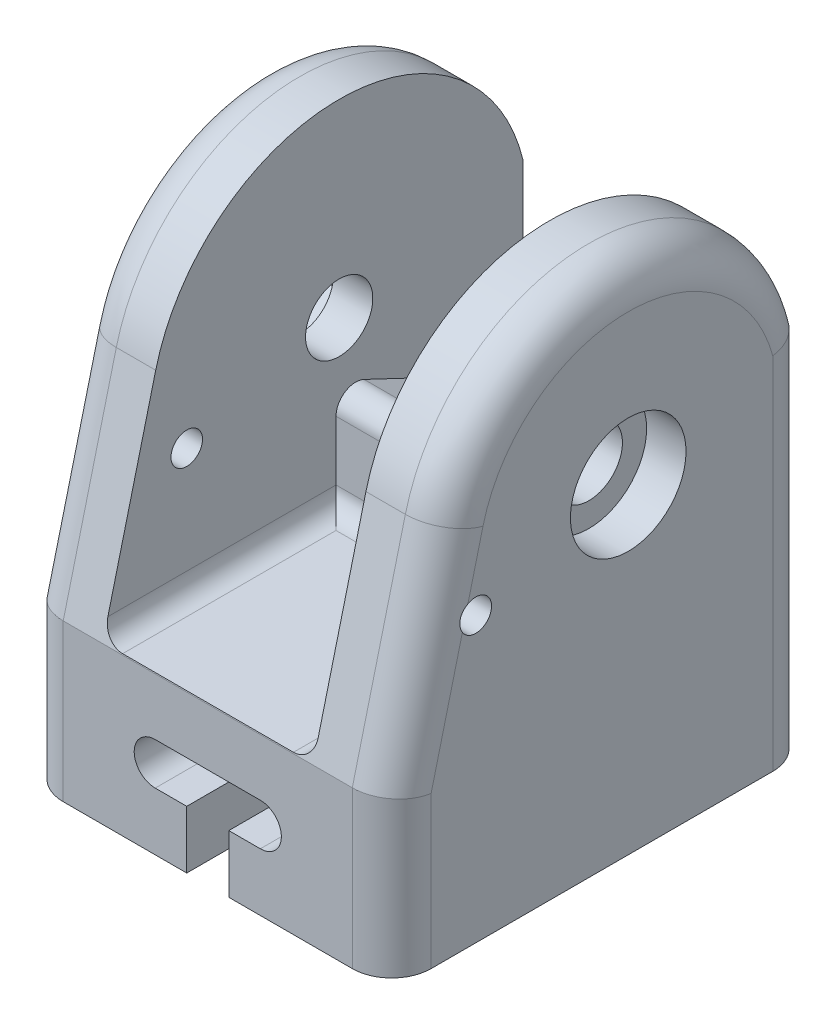
SolidWorks part; units mm, degrees
ref_plane "Front Plane" through (0, 0, 0) normal (0, 0, 1) x (1, 0, 0)
ref_plane "Top Plane" through (0, 0, 0) normal (0, 1, 0) x (1, 0, 0)
ref_plane "Right Plane" through (0, 0, 0) normal (1, 0, 0) x (0, 0, -1)
sketch "Sketch2" plane through (0, 0, 0) normal (0, 1, 0) x (1, 0, 0)
  line L0 (5, 10) -> (8.75, 10)
  line L1 (-8.75, -10) -> (8.75, -10)
  line L2 (-8.75, -10) -> (-8.75, 10)
  line L3 (-8.75, 10) -> (-5, 10)
  line L4 (8.75, -10) -> (8.75, 10)
  line L5 (-8.75, -10) -> (8.75, 10) construction
  line L6 (-8.75, 10) -> (8.75, -10) construction
  line L8 (-5, 10) -> (-5, 5)
  line L9 (-5, 5) -> (5, 5)
  line L10 (5, 10) -> (5, 5)
  point P0 (0, 0)
  point P15 (-5, 5)
  dimension "D1" = 17.5
  dimension "D2" = 20
  dimension "D3" = 3.75
  dimension "D4" = 5
extrude "Boss-Extrude1" add sketch "Sketch2" along normal blind 22.5
sketch "Sketch3" plane through (0, 22.5, 0) normal (0, 1, 0) x (1, 0, 0)
  line L0 (-8.75, -10) -> (8.75, -10) construction
  line L1 (-5, 10) -> (5, 10)
  line L2 (-5, 10) -> (-5, -10)
  line L3 (-5, -10) -> (5, -10)
  line L4 (5, 10) -> (5, -10)
  line L5 (5, 10) -> (5, 5) construction
extrude "Cut-Extrude1" cut sketch "Sketch3" against normal blind 17.5
sketch "Sketch4" plane through (8.75, 0, 0) normal (1, 0, 0) x (0, 0, -1)
  line L0 (10, 22.5) -> (10, 0) construction
  line L1 (-10, 22.5) -> (10, 22.5) construction
  line L2 (10, 14.8565) -> (10, 0)
  line L3 (10, 0) -> (-10, 0)
  line L4 (-10, 0) -> (-10, 4.9522)
  line L5 (1.25, 12.75) -> (-6, 11) construction
  line L6 (-10, 4.9522) -> (-7.4764, 14.9522)
  line L7 (-10, 22.5) -> (-10, 0) construction
  line L8 (1.25, 12.75) -> (-10, 12.75) construction
  circle A0 centre (1.25, 12.75) radius 1.6
  arc A1 (10, 14.8565) -> (-7.4764, 14.9522) centre (1.25, 12.75) ccw
  circle A2 centre (-6, 11) radius 0.75
  dimension "D1" = 8.75
  dimension "D4" = 3.2
  dimension "D7" = 9
  dimension "D6" = 1.75
  dimension "D8" = 1.5
  dimension "D2" = 9.75
  dimension "D3" = 10
  dimension "D5" = 4
  dimension "D9" = 7.25
  dimension "D10" = 13.57
extrude "Cut-Extrude2" cut sketch "Sketch4" against normal through all flip side to cut
fillet "Fillet1" radius 1.875 8 edges at (-8.75, 9.9522, 8.7382) (8.75, 9.9522, 8.7382) (-8.75, 7.4283, -10) (8.75, 7.4283, -10) (-8.75, 2.4761, 10) (8.75, 2.4761, 10) (-8.75, 21.7499, -1.2993) (8.75, 21.7499, -1.2993)
sketch "Sketch7" plane through (8.75, 0, 0) normal (1, 0, 0) x (0, 0, -1)
  line L1 (-10, 0) -> (10, 0)
  line L2 (-10, 0) -> (-10, 25)
  line L3 (-10, 25) -> (10, 25)
  line L4 (10, 0) -> (10, 25)
  dimension "D1" = 25
  dimension "D2" = 20
extrude "Cut-Extrude4" cut sketch "Sketch7" against normal blind 8.75
sketch "Sketch8" plane through (-5, 0, 0) normal (1, 0, 0) x (0, 0, -1)
  line L0 (5, 5) -> (5, 8.4)
  line L2 (5, 8.4) -> (1.1, 10.25)
  line L3 (1.1, 10.25) -> (1.1, 5)
  line L4 (5, 5) -> (-9.9879, 5) construction
  line L5 (1.1, 5) -> (5, 5)
  line L7 (5, 5) -> (5, 0) construction
  dimension "D1" = 3.4
  dimension "D2" = 5.25
  dimension "D3" = 3.9
extrude "Boss-Extrude3" add sketch "Sketch8" along normal up to surface (5 mm away) up to face at (0, 2.9904, 3.9976)
fillet "Fillet2" radius 0.9375 4 edges at (-2.5, 8.4, -5) (-2.5, 10.25, -1.1) (-2.5, 5, -1.1) (-5, 5, 4.444)
mirror "Mirror2" about plane through (0, 0, 0) normal (-1, 0, 0) of bodies 108
sketch "Sketch11" plane through (8.75, 0, 0) normal (1, 0, 0) x (0, 0, -1)
  circle A0 centre (1.25, 12.75) radius 2.75
  dimension "D1" = 5.5
extrude "Cut-Extrude6" cut sketch "Sketch11" against normal blind 1.875
sketch "Sketch12" plane through (-8.75, 0, 0) normal (-1, 0, 0) x (0, 0, 1)
  line L1 (-1.25, 15.9254) -> (-4, 14.3377)
  line L2 (-4, 14.3377) -> (-4, 11.1623)
  line L3 (-4, 11.1623) -> (-1.25, 9.5746)
  line L4 (-1.25, 9.5746) -> (1.5, 11.1623)
  line L5 (1.5, 11.1623) -> (1.5, 14.3377)
  line L6 (1.5, 14.3377) -> (-1.25, 15.9254)
  circle A0 centre (-1.25, 12.75) radius 2.75 construction
  dimension "D1" = 5.5
extrude "Cut-Extrude7" cut sketch "Sketch12" against normal blind 1.875
sketch "Sketch13" plane through (-8.75, 0, 0) normal (-1, 0, 0) x (0, 0, 1)
  text T0 "I" font "Century Schoolbook" height in points 36
extrude "Boss-Extrude4" add sketch "Sketch13" along normal blind 0.2
sketch "Sketch14" [suppressed] plane through (-8.75, 0, 0) normal (-1, 0, 0) x (0, 0, 1)
  text T0 "M" font "Century Schoolbook" height in points 36
extrude "Boss-Extrude5" [suppressed] add sketch "Sketch14" along normal blind 0.2
sketch "Sketch16" [suppressed] plane through (-8.75, 0, 0) normal (-1, 0, 0) x (0, 0, 1)
  text T0 "R" font "Century Schoolbook" height in points 36
extrude "Boss-Extrude6" [suppressed] add sketch "Sketch16" along normal blind 0.2
sketch "Sketch17" [suppressed] plane through (-8.75, 0, 0) normal (-1, 0, 0) x (0, 0, 1)
  text T0 "P" font "Century Schoolbook" height in points 36
extrude "Boss-Extrude7" [suppressed] add sketch "Sketch17" along normal blind 0.2
sketch "Sketch18" [suppressed] plane through (-8.75, 0, 0) normal (-1, 0, 0) x (0, 0, 1)
  text T0 "T" font "Century Schoolbook" height in points 36
extrude "Boss-Extrude8" [suppressed] add sketch "Sketch18" along normal blind 0.2
sketch "Sketch19" plane through (0, 0, 0) normal (0, -1, 0) x (1, 0, 0)
  line L0 (-8.75, 2.0489) -> (-8.75, -2.1695)
  line L12 (-5, -5) -> (5, -5)
  line L13 (5, -5) -> (5, -10)
  line L14 (5, -10) -> (6.875, -10)
  line L15 (8.75, -8.125) -> (8.75, 8.125)
  line L16 (6.875, 10) -> (-6.875, 10)
  line L17 (-8.75, 8.125) -> (-8.75, 2.0489)
  line L18 (-8.75, 2.0489) -> (-8.95, 2.0489)
  line L19 (-8.95, 2.0489) -> (-8.95, -2.1695)
  line L20 (-8.95, -2.1695) -> (-8.75, -2.1695)
  line L21 (-8.75, -2.1695) -> (-8.75, -8.125)
  line L22 (-6.875, -10) -> (-5, -10)
  line L23 (-5, -10) -> (-5, -5)
  line L24 (-5, -5) -> (5, -5)
  line L25 (5, -5) -> (5, -10)
  line L26 (5, -10) -> (6.875, -10)
  line L27 (8.75, -8.125) -> (8.75, 8.125)
  line L28 (6.875, 10) -> (-6.875, 10)
  line L29 (-8.75, 8.125) -> (-8.75, 2.0489)
  line L33 (-8.75, -2.1695) -> (-8.75, -8.125)
  line L34 (-6.875, -10) -> (-5, -10)
  line L35 (-5, -10) -> (-5, -5)
  arc A4 (6.875, -10) -> (8.75, -8.125) centre (6.875, -8.125) ccw
  arc A5 (8.75, 8.125) -> (6.875, 10) centre (6.875, 8.125) ccw
  arc A6 (-6.875, 10) -> (-8.75, 8.125) centre (-6.875, 8.125) ccw
  arc A7 (-8.75, -8.125) -> (-6.875, -10) centre (-6.875, -8.125) ccw
  arc A8 (6.875, -10) -> (8.75, -8.125) centre (6.875, -8.125) ccw
  arc A9 (8.75, 8.125) -> (6.875, 10) centre (6.875, 8.125) ccw
  arc A10 (-6.875, 10) -> (-8.75, 8.125) centre (-6.875, 8.125) ccw
  arc A11 (-8.75, -8.125) -> (-6.875, -10) centre (-6.875, -8.125) ccw
  dimension "D1" = 0
extrude "Boss-Extrude9" add sketch "Sketch19" along normal blind 2.5
sketch "Sketch20" plane through (0, 0, -5) normal (0, 0, -1) x (-1, 0, 0)
  line L0 (1, 0.25) -> (2.5, 0.25)
  line L1 (5, 7.8071) -> (5, -2.5) construction
  line L6 (-2.5, 1.25) -> (2.5, 1.25) construction
  line L7 (-2.5, 2.25) -> (2.5, 2.25)
  line L8 (-2.5, 0.25) -> (-1, 0.25)
  line L9 (0, 1.25) -> (0, -2.5) construction
  line L10 (1, 0.25) -> (1, -2.5)
  line L11 (-1, 0.25) -> (-1, -2.5)
  line L12 (5, 7.8071) -> (-5, 7.8071) construction
  arc A2 (-2.5, 2.25) -> (-2.5, 0.25) centre (-2.5, 1.25) ccw
  arc A3 (2.5, 0.25) -> (2.5, 2.25) centre (2.5, 1.25) ccw
  arc A5 (-1, -2.5) -> (1, -2.5) centre (0, -2.5) ccw
  point P5 (0, 1.25)
  point P8 (0, 1.25)
  point P14 (0, -0.625)
  dimension "D1" = 3.75
  dimension "D2" = 1
  dimension "D3" = 5
  dimension "D4" = 6.5571
extrude "Cut-Extrude8" cut sketch "Sketch20" against normal through all
